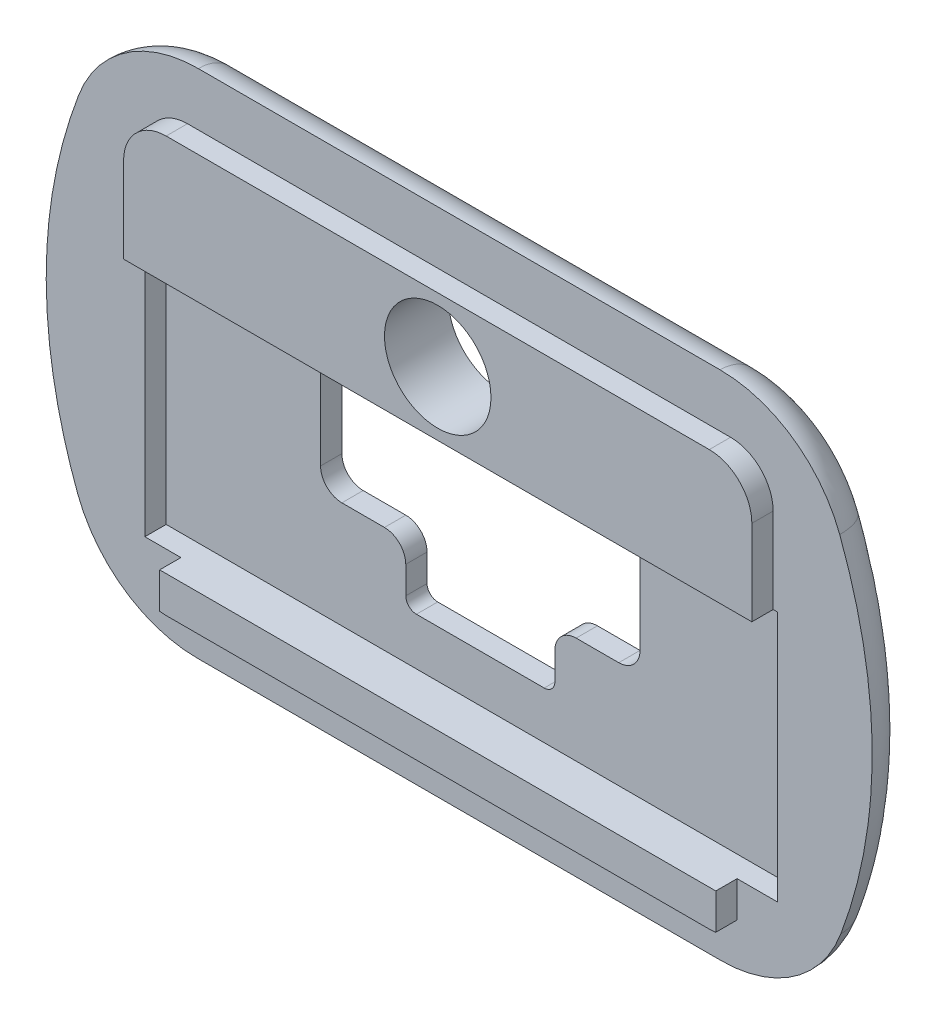
SolidWorks part; units mm, degrees
ref_plane "Front Plane" through (0, 0, 0) normal (0, 0, 1) x (1, 0, 0)
ref_plane "Top Plane" through (0, 0, 0) normal (0, 1, 0) x (1, 0, 0)
ref_plane "Right Plane" through (0, 0, 0) normal (1, 0, 0) x (0, 0, -1)
sketch "Sketch1" plane through (0, 0, 0) normal (0, 0, 1) x (1, 0, 0)
  line L0 (-11.9284, 3.1923) -> (13.5716, 3.1923)
  line L1 (-13.9284, 6.9272) -> (-13.9284, 20.6923)
  line L2 (-11.9284, 22.6923) -> (13.5716, 22.6923)
  line L3 (15.5716, 6.9272) -> (15.5716, 20.6923)
  line L4 (-13.9284, 22.6923) -> (0.9376, 12.8656) construction
  line L7 (-17.0825, 24.7341) -> (-13.2392, 22.2028) construction
  line L8 (0.8216, 1.1923) -> (0.8216, 25.1923) construction
  line L9 (0.8216, 25.1923) -> (0.8216, 3.1923) construction
  line L10 (14.5325, 3.8791) -> (15.5716, 3.1923) construction
  line L11 (0.9376, 12.8656) -> (17.6599, 1.8519) construction
  line L28 (-13.9284, 6.9272) -> (-12.7351, 6.9272)
  line L34 (0.8216, 21.9694) -> (0.8216, 1.9694) construction
  line L35 (-12.2351, 6.4272) -> (-12.2351, 3.2159)
  line L37 (15.5716, 6.9272) -> (14.3784, 6.9272)
  line L38 (13.8784, 6.4272) -> (13.8784, 3.2159)
  arc A0 (13.8784, 3.2159) -> (13.5716, 3.1923) centre (13.5716, 5.1923) cw
  arc A1 (-12.2351, 3.2159) -> (-11.9284, 3.1923) centre (-11.9284, 5.1923) ccw
  arc A2 (-11.9284, 22.6923) -> (-13.9284, 20.6923) centre (-11.9284, 20.6923) ccw
  arc A3 (13.5716, 22.6923) -> (15.5716, 20.6923) centre (13.5716, 20.6923) cw
  arc A18 (-12.7351, 6.9272) -> (-12.2351, 6.4272) centre (-12.7351, 6.4272) cw
  arc A19 (14.3784, 6.9272) -> (13.8784, 6.4272) centre (14.3784, 6.4272) ccw
  point P20 (-12.2351, 22.6923)
  dimension "D5" = 2
  dimension "D6" = 0.5
  dimension "D2" = 29.5
  dimension "D4" = 19.5
sketch "Sketch2" plane through (0, 0, 0) normal (0, 0, 1) x (1, 0, 0)
  line L0 (-2.1784, 7.121) -> (3.8216, 7.121)
  line L1 (-5.6784, 15.9243) -> (7.3216, 15.9243)
  line L2 (-2.6784, 7.621) -> (-2.6784, 8.901)
  line L3 (-6.6784, 14.9243) -> (-6.6784, 10.901)
  line L4 (-5.6784, 9.901) -> (-3.6784, 9.901)
  line L5 (7.3216, 9.901) -> (5.3216, 9.901)
  line L6 (8.3216, 14.9243) -> (8.3216, 10.901)
  line L7 (4.3216, 7.621) -> (4.3216, 8.901)
  line L8 (0.8216, 15.9243) -> (0.8216, 7.121) construction
  line L9 (8.3216, 12.9126) -> (-6.6784, 12.9126) construction
  arc A0 (-2.6784, 8.901) -> (-3.6784, 9.901) centre (-3.6784, 8.901) ccw
  arc A1 (5.3216, 9.901) -> (4.3216, 8.901) centre (5.3216, 8.901) ccw
  arc A2 (-6.6784, 10.901) -> (-5.6784, 9.901) centre (-5.6784, 10.901) ccw
  arc A3 (7.3216, 9.901) -> (8.3216, 10.901) centre (7.3216, 10.901) ccw
  arc A4 (-6.6784, 14.9243) -> (-5.6784, 15.9243) centre (-5.6784, 14.9243) cw
  arc A5 (7.3216, 15.9243) -> (8.3216, 14.9243) centre (7.3216, 14.9243) cw
  arc A6 (-2.1784, 7.121) -> (-2.6784, 7.621) centre (-2.1784, 7.621) cw
  arc A7 (4.3216, 7.621) -> (3.8216, 7.121) centre (3.8216, 7.621) cw
  point P0 (3.0945, 14.452)
  point P1 (3.0945, 14.452)
  point P3 (3.0945, 14.452)
  point P5 (0.8216, 7.121)
  point P8 (0.8216, 15.9243)
  point P17 (0.8216, 12.9126)
  point P30 (-6.6784, 15.9243)
  point P33 (8.3216, 15.9243)
  dimension "D2" = 1
  dimension "D3" = 0.5
  dimension "D1" = 15
sketch "Sketch4" plane through (0, 0, 0) normal (0, 0, 1) x (1, 0, 0)
  line L0 (-11.47, 1.1896) -> (13.1295, 1.1896)
  line L1 (-11.4218, 25.1896) -> (13.0813, 25.1896)
  arc A0 (-11.4218, 25.1896) -> (-17.0387, 21.2993) centre (-11.4218, 19.1896) ccw
  arc A1 (-11.47, 1.1896) -> (-17.0866, 5.0793) centre (-11.47, 7.1896) cw
  arc A2 (13.0813, 25.1896) -> (18.6982, 21.2993) centre (13.0813, 19.1896) cw
  arc A3 (13.1295, 1.1896) -> (18.7461, 5.0793) centre (13.1295, 7.1896) ccw
  spline S0 degree 3 poles (-17.0866, 5.0793) (-18.0777, 7.717) (-19.0613, 13.218) (-18.0465, 18.6161) (-17.0387, 21.2993) knots 0.167422 0.167422 0.167422 0.167422 0.502499 0.837905 0.837905 0.837905 0.837905
  spline S1 degree 3 poles (18.7461, 5.0793) (19.7372, 7.717) (20.7208, 13.218) (19.706, 18.6161) (18.6982, 21.2993) knots 0.167422 0.167422 0.167422 0.167422 0.502499 0.837905 0.837905 0.837905 0.837905
extrude "Boss-Extrude1" add sketch "Sketch4" along normal blind 2
extrude "Boss-Extrude2" add sketch "Sketch1" along normal blind 3
extrude "Cut-Extrude3" cut sketch "Sketch2" along normal blind 3
sketch "Sketch6" plane through (0, 0, 3) normal (0, 0, 1) x (1, 0, 0)
  circle A0 centre (0.8216, 19.6851) radius 2.5
  dimension "D1" = 5
sketch "Sketch7" plane through (0, 0, 3) normal (0, 0, 1) x (1, 0, 0)
  line L0 (-13.9284, 20.6923) -> (-13.9284, 6.9272) construction
  line L1 (-13.9284, 16.6874) -> (15.7858, 16.6874)
  line L2 (-13.9284, 16.6874) -> (-13.9284, 4.8974)
  line L3 (-13.9284, 4.8974) -> (15.7858, 4.8974)
  line L4 (15.7858, 16.6874) -> (15.7858, 4.8974)
extrude "Cut-Extrude4" cut sketch "Sketch7" against normal blind 2
extrude "Cut-Extrude5" cut sketch "Sketch6" against normal through all both and the other way through all contours A0
fillet "Fillet1" radius 2 8 edges at (0.8297, 1.1896, 0) (0.8297, 25.1896, 0) (16.4976, 24.1221, 0) (16.5455, 2.257, 0) (-14.886, 2.257, 0) (-14.8381, 24.1221, 0)
